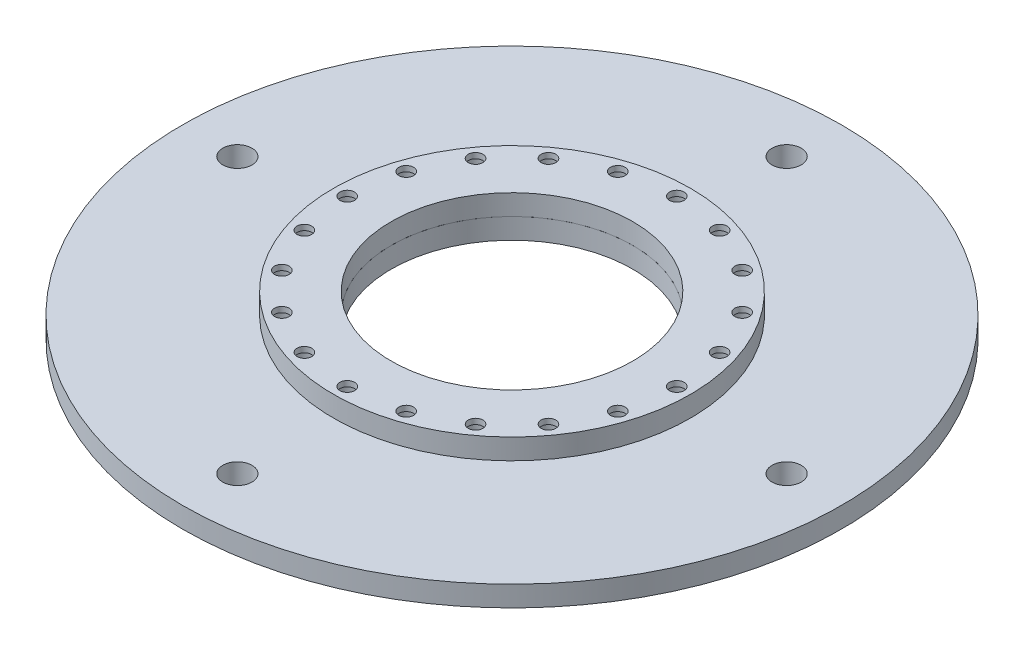
SolidWorks part; units mm, degrees
material "Plain Carbon Steel"
ref_plane "Front Plane" through (0, 0, 0) normal (0, 0, 1) x (1, 0, 0)
ref_plane "Top Plane" through (0, 0, 0) normal (0, 1, 0) x (1, 0, 0)
ref_plane "Right Plane" through (0, 0, 0) normal (1, 0, 0) x (0, 0, -1)
sketch "Sketch9" plane through (0, 0, 0) normal (0, 1, 0) x (1, 0, 0)
  circle A2 centre (0, 0) radius 82.55
  circle A4 centre (0, 0) radius 55.88
  circle A5 centre (0, 0) radius 76.2 construction
  point P6 (0, 76.2)
  point P34 (0, 0)
  dimension "Diameter_BackPlate" = 165.1
  dimension "Diameter_FuelOuterPlenum" = 111.76
  dimension "Diameter_BackPlate_BoltCircle" = 152.4
extrude "REF_BackPlate" add sketch "Sketch9" along normal blind 9.525 contours A2 A4 region at (-80.2151, 0, 0)
sketch "Sketch1" plane through (0, 0, 0) normal (0, 1, 0) x (1, 0, 0)
  line L1 (0, 82.55) -> (0, 81.788) construction
  line L2 (0, 81.788) -> (0, 76.2) construction
  line L6 (8.7416, 55.192) -> (11.0014, 69.4604) construction
  line L7 (0, 82.55) -> (0, 127) construction
  line L8 (39.2452, 120.7842) -> (25.5094, 78.5097) construction
  line L9 (8.7416, 55.192) -> (0, 0) construction
  circle A3 centre (0, 0) radius 152.4
  circle A8 centre (0, 0) radius 127 construction
  circle A14 centre (0, 76.2) radius 5.588 construction
  circle A15 centre (0, 0) radius 55.88 construction
  circle A17 centre (0, 0) radius 82.55 construction
  circle A18 centre (23.5471, 72.4705) radius 5.588 construction
  circle A19 centre (0, 0) radius 76.2 construction
  circle A20 centre (0, 0) radius 55.88
  circle A23 centre (0, 0) radius 70.3262 construction
  arc A24 (0, 76.2) -> (23.5471, 72.4705) centre (0, 0) cw construction
  point P2 (0, 127)
  point P5 (0, 70.3262)
  point P12 (11.9203, 75.2619)
  dimension "Diameter_Takeout_BoltCircle" = 254
  dimension "Diameter_ThrustPlate" = 304.8
  dimension "D1" = 11.176
  dimension "D2" = 140.6525
  dimension "D3" = 18
sketch "Sketch20" plane through (0, 0, 0) normal (0, -1, 0) x (-1, 0, 0)
  point P0 (0, 76.2)
hole_wizard "REF_CBORE_BackPlate" positions "Sketch20" profile "Sketch21" counterbore size "1/4" standard "ANSI Inch" end condition through all
sketch "Sketch21" plane through (0, 0, -76.2) normal (1, 0, 0) x (0, 0, -1)
  line L0 (0, 0) -> (0, 9.525)
  line L1 (0, 9.525) -> (3.3782, 9.525)
  line L3 (3.3782, 9.525) -> (3.3782, 6.985)
  line L4 (3.3782, 6.985) -> (5.588, 6.985)
  line L5 (5.588, 6.985) -> (5.588, 0)
  line L7 (5.588, 0) -> (0, 0)
  line L11 (0, -6.35) -> (0, 107.95) construction
  dimension "Thru Hole Dia." = 6.7564
  dimension "Thru Hole Depth" = 9.525
  dimension "C'Bore Dia." = 11.176
  dimension "C'Bore Depth" = 6.985
pattern_circular "REF_CBORE_BackPlate_Pattern" count 20 over 360 about axis through (0, 9.525, 0) along (0, -1, 0) of "REF_CBORE_BackPlate"
extrude "ThrustPlate_TC3" add sketch "Sketch1" against normal blind 9.525 separate body contours A3 region at (-148.0895, 0, 0)
sketch "Sketch11" plane through (0, 0, 0) normal (0, 1, 0) x (1, 0, 0)
  point P0 (0, 127)
hole_wizard "UNDEF_Clearance_ThrustPlate" positions "Sketch11" profile "Sketch12" hole size "1/2" standard "ANSI Inch" end condition through all
sketch "Sketch12" plane through (0, 0, -127) normal (1, 0, 0) x (0, 0, 1)
  line L0 (0, 0) -> (0, 9.525)
  line L1 (0, 9.525) -> (6.7462, 9.525)
  line L2 (6.7462, 9.525) -> (6.7462, 0)
  line L5 (6.7462, 0) -> (0, 0)
  line L11 (0, -6.35) -> (0, 107.95) construction
  dimension "Thru Hole Dia." = 13.4925
  dimension "Thru Hole Depth" = 9.525
pattern_circular "Clearance_ThrustPlate_Pattern" count 4 over 360 about axis through (0, -9.525, 0) along (0, 1, 0) of "UNDEF_Clearance_ThrustPlate" reverse direction yes
sketch "Sketch22" plane through (0, 0, 0) normal (0, 1, 0) x (1, 0, 0)
  point P0 (0, 70.3262)
hole_wizard "#10 Clearance Hole1" positions "Sketch22" profile "Sketch23" hole size "#10" standard "ANSI Inch" end condition through all
sketch "Sketch23" plane through (0, 0, -70.3262) normal (1, 0, 0) x (0, 0, 1)
  line L0 (0, 0) -> (0, 9.525)
  line L1 (0, 9.525) -> (2.5527, 9.525)
  line L2 (2.5527, 9.525) -> (2.5527, 0)
  line L5 (2.5527, 0) -> (0, 0)
  line L11 (0, -6.35) -> (0, 107.95) construction
  dimension "Thru Hole Dia." = 5.1054
  dimension "Thru Hole Depth" = 9.525
pattern_circular "CirPattern1" count 10 over 360 about axis through (0, -9.525, 0) along (0, 1, 0) of "#10 Clearance Hole1" reverse direction yes
equation "\"Diameter_BackPlate\"= 6.5"
equation "\"VAR_Diameter_BackPlate_BoltCircle\"= 6"
equation "\"VAR_Diameter_FuelOuterPlenum\"= 4.4"
equation "\"Diameter_BackPlate@Sketch9\"=\"Diameter_BackPlate\""
equation "\"Diameter_BackPlate_BoltCircle@Sketch9\"=\"VAR_Diameter_BackPlate_BoltCircle\""
equation "\"Diameter_FuelOuterPlenum@Sketch9\"=\"VAR_Diameter_FuelOuterPlenum\""
equation "\"Thickness_ThrustPlate\"= 0.375'undetermined"
equation "\"Diameter_ThrustPlate\"= 12'defined"
equation "\"Diameter_Takeout_BoltCicle\"= 10'defined"
equation "\"Diameter_Takeout_BoltCircle@Sketch1\"=\"Diameter_Takeout_BoltCicle\""
equation "\"Diameter_ThrustPlate@Sketch1\"=\"Diameter_ThrustPlate\""
equation "\"D1@ThrustPlate_TC3\"=\"Thickness_ThrustPlate\""
equation "\"VAR_Diameter_CBORE\"= 0.44'undetermined"
equation "\"VAR_Diameter_Clearance_ThrustPlate\"= 0.25'undetermined"
equation "\"D3@Sketch1\"=360/\"D1@REF_CBORE_BackPlate_Pattern\""
equation "\"D1@Sketch1\"=\"C'Bore Dia.@Sketch21\"''''''''''''''''''''''''''''''''''''''''''''''''"
equation "\"C'Bore Dia.@Sketch21\"=\"VAR_Diameter_CBORE\""
equation "\"NumberBolts_BackPlate\"= 20"
equation "\"NumberBolts_Takeout\"= 4'defined"
equation "\"D1@Clearance_ThrustPlate_Pattern\"=\"NumberBolts_Takeout\""
equation "\"D1@REF_CBORE_BackPlate_Pattern\"=\"NumberBolts_BackPlate\""
